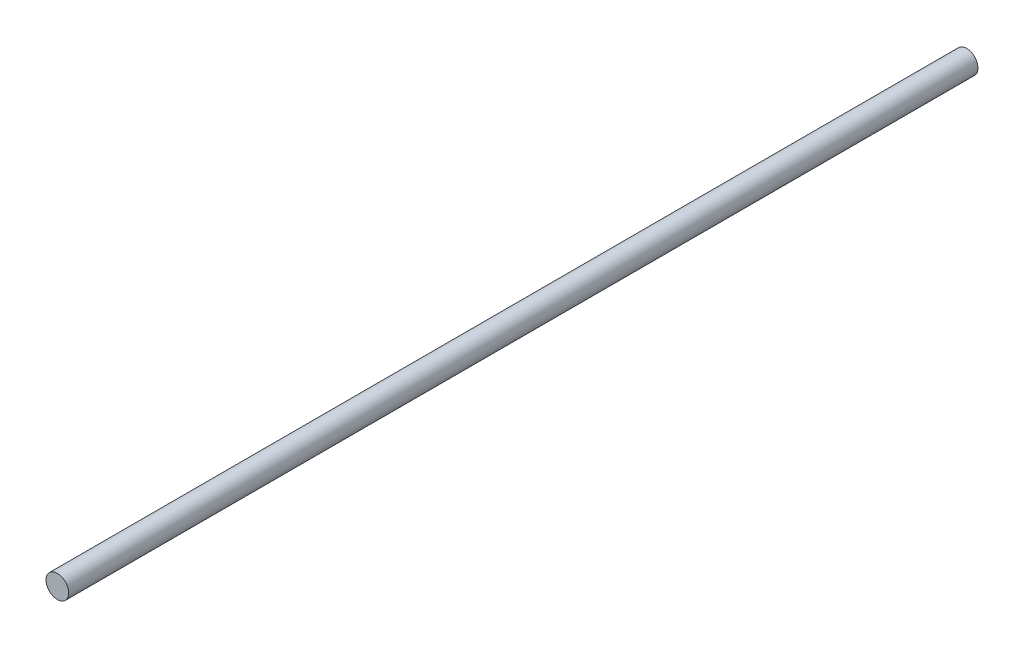
SolidWorks part; units mm, degrees
material "AISI 1010 Steel, hot rolled bar"
ref_plane "Front Plane" through (0, 0, 0) normal (0, 0, 1) x (1, 0, 0)
ref_plane "Top Plane" through (0, 0, 0) normal (0, 1, 0) x (1, 0, 0)
ref_plane "Right Plane" through (0, 0, 0) normal (1, 0, 0) x (0, 0, -1)
sketch "Sketch1" plane through (0, 0, 0) normal (0, 0, 1) x (1, 0, 0)
  circle A0 centre (0, 0) radius 5
  dimension "D1" = 10
extrude "Boss-Extrude1" add sketch "Sketch1" along normal mid plane 400
